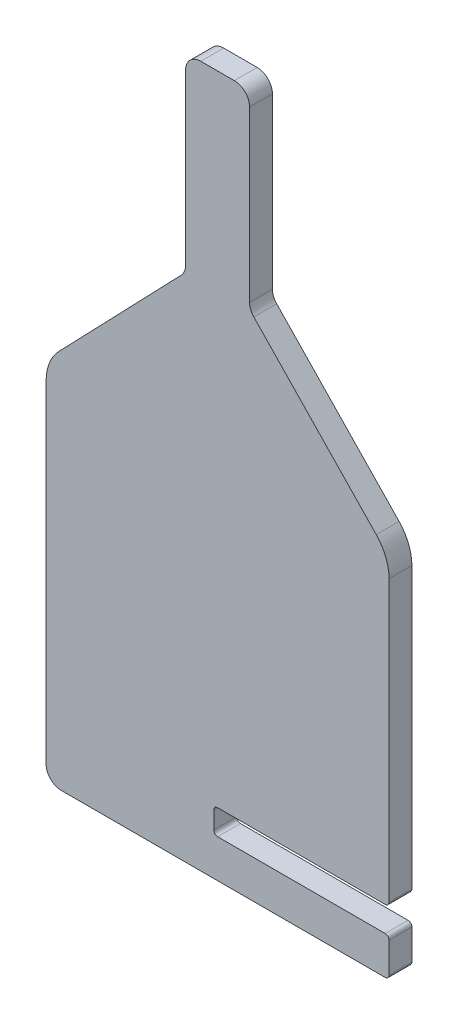
SolidWorks part; units mm, degrees
ref_plane "Alzado" through (0, 0, 0) normal (0, 0, 1) x (1, 0, 0)
ref_plane "Planta" through (0, 0, 0) normal (0, 1, 0) x (1, 0, 0)
ref_plane "Vista lateral" through (0, 0, 0) normal (1, 0, 0) x (0, 0, -1)
sketch "Croquis1" plane through (0, 0, 0) normal (0, 0, 1) x (1, 0, 0)
  line L0 (-4.2, 20) -> (-22.5, 0.9719)
  line L1 (-4.2, 45) -> (4.2, 45)
  line L2 (-22.5, 0.9719) -> (-22.5, -47.0281)
  line L3 (-22.5, -47.0281) -> (22.5, -47.0281)
  line L4 (22.5, 0.9719) -> (22.5, -47.0281)
  line L5 (-4.2, 45) -> (4.2, 45)
  line L6 (-4.2, 45) -> (-4.2, 20)
  line L8 (4.2, 45) -> (4.2, 19.999)
  line L9 (4.2, 19.999) -> (22.5, 0.9719)
  line L10 (0, 72.8664) -> (0, -82.626) construction
  dimension "D1" = 45
  dimension "D2" = 25
  dimension "D3" = 4.2
  dimension "D4" = 22.5
  dimension "D5" = 45
  dimension "D6" = 4.2
  dimension "D7" = 26.3993
  dimension "D8" = 26.4
  dimension "D9" = 48
  dimension "D10" = 48
extrude "Saliente-Extruir1" add sketch "Croquis1" along normal blind 3 contours L6 L0 L2 L3 L4 L9 L8 L1
sketch "Croquis3" plane through (0, 0, 3) normal (0, 0, 1) x (1, 0, 0)
  line L0 (22.5, 0.9719) -> (22.5, -47.0281) construction
  line L1 (22.5, -38.7281) -> (-0.5, -38.7281)
  line L2 (22.5, -38.7281) -> (22.5, -42.0281)
  line L3 (22.5, -42.0281) -> (-0.5, -42.0281)
  line L4 (-0.5, -38.7281) -> (-0.5, -42.0281)
  line L5 (-22.5, -47.0281) -> (22.5, -47.0281) construction
  dimension "D1" = 3.3
  dimension "D2" = 5
  dimension "D3" = 23
extrude "Cortar-Extruir2" cut sketch "Croquis3" against normal up to surface (3 mm away) up to face at (0, 4.7358, 0)
fillet "Redondeo1" radius 2 5 edges at (-22.5, -47.0281, 1.5) (-4.2, 20, 1.5) (-4.2, 45, 1.5) (4.2, 19.999, 1.5) (4.2, 45, 1.5)
fillet "Redondeo2" radius 6 2 edges at (-22.5, 0.9719, 1.5) (22.5, 0.9719, 1.5)
fillet "Redondeo3" radius 0.5 5 edges at (22.5, -47.0281, 1.5) (-0.5, -42.0281, 1.5) (-0.5, -38.7281, 1.5) (22.5, -38.7281, 1.5) (22.5, -42.0281, 1.5)
